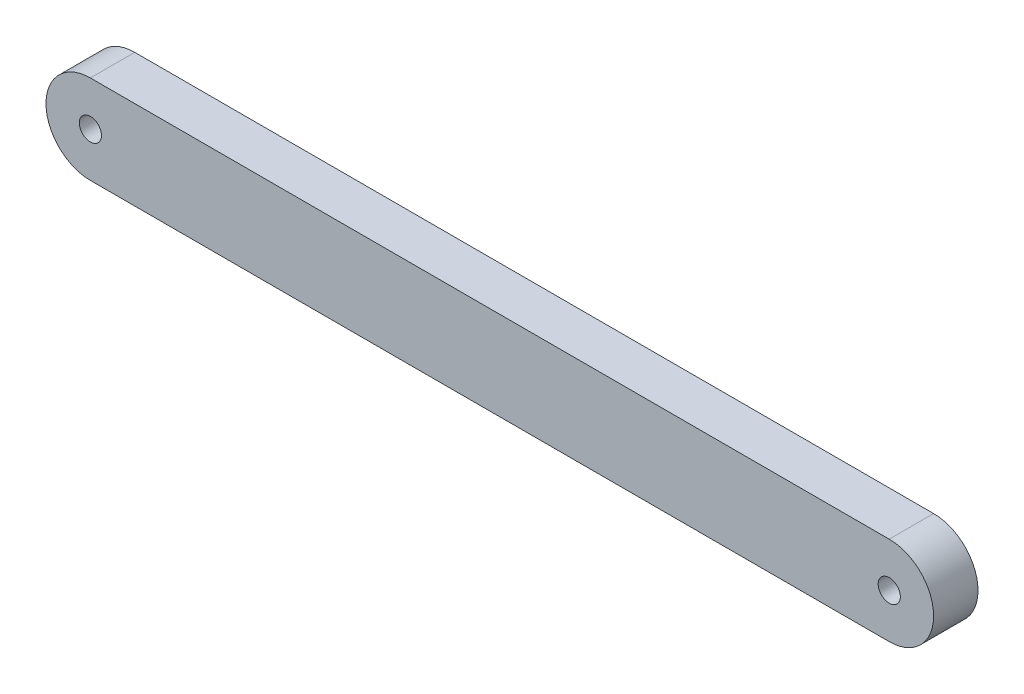
SolidWorks part; units mm, degrees
ref_plane "Front Plane" through (0, 0, 0) normal (0, 0, 1) x (1, 0, 0)
ref_plane "Top Plane" through (0, 0, 0) normal (0, 1, 0) x (1, 0, 0)
ref_plane "Right Plane" through (0, 0, 0) normal (1, 0, 0) x (0, 0, -1)
sketch "Sketch1" plane through (0, 0, 0) normal (0, 0, 1) x (1, 0, 0)
  line L0 (0, 10) -> (180, 10)
  line L1 (180, -10) -> (0, -10)
  circle A0 centre (0, 0) radius 2.5
  circle A1 centre (180, 0) radius 2.5
  arc A2 (0, -10) -> (0, 10) centre (0, 0) cw
  arc A3 (180, -10) -> (180, 10) centre (180, 0) ccw
  point P9 (-10, 0)
  point P10 (0, 0)
  point P11 (0, 0)
  dimension "D2" = 5
  dimension "D3" = 10
  dimension "D1" = 180
extrude "Boss-Extrude1" add sketch "Sketch1" along normal blind 10
